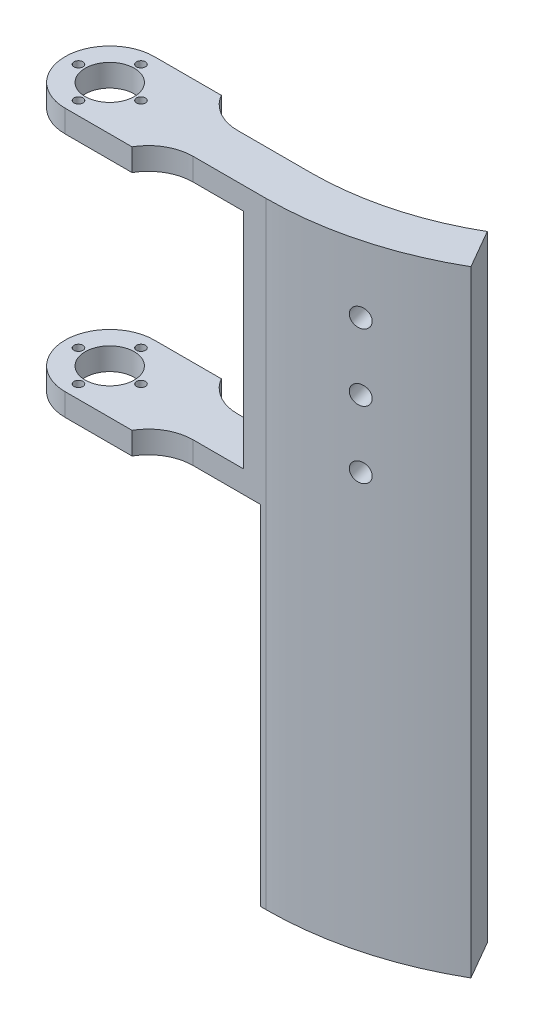
SolidWorks part; units mm, degrees
ref_plane "Front Plane" through (0, 0, 0) normal (0, 0, 1) x (1, 0, 0)
ref_plane "Top Plane" through (0, 0, 0) normal (0, 1, 0) x (1, 0, 0)
ref_plane "Right Plane" through (0, 0, 0) normal (1, 0, 0) x (0, 0, -1)
sketch "Sketch1" plane through (0, 0, 0) normal (0, 0, 1) x (1, 0, 0)
  line L0 (-25, 30) -> (25, 30)
  line L1 (-20, 25) -> (20, 25)
  line L3 (-20, -25) -> (20, -25)
  line L4 (20, 25) -> (20, -25)
  line L5 (-20, 25) -> (20, -25) construction
  line L6 (-20, -25) -> (20, 25) construction
  line L7 (25, 30) -> (25, -30)
  line L8 (-25, -30) -> (25, -30)
  line L9 (-25, 30) -> (-25, 25)
  line L10 (-20, 25) -> (-25, 25)
  line L11 (-20, -25) -> (-25, -25)
  line L12 (-25, -25) -> (-25, -30)
  line L13 (-25, 30) -> (-25, -30) construction
  line L14 (-20, 25) -> (-20, -25) construction
  point P0 (0, 0)
  dimension "D1" = 40
  dimension "D2" = 50
  dimension "D3" = 5
extrude "Boss-Extrude2" add sketch "Sketch1" along normal blind 20
fillet "Fillet1" 2 edges at (-25, 27.5, 20) (-25, 27.5, 0) type full round first side face at (-1.25, 0, 20) second side face at (-1.25, 0, 0) middle face at (-25, 27.5, 10)
fillet "Fillet2" 2 edges at (-25, -27.5, 20) (-25, -27.5, 0) type full round first side face at (1.25, 0, 20) second side face at (1.25, 0, 0) middle face at (-25, -27.5, 10)
sketch "Sketch5" plane through (0, 30, 0) normal (0, 1, 0) x (1, 0, 0)
  circle A0 centre (-15, -10) radius 7 construction
  circle A1 centre (-15, -3) radius 1
  circle A2 centre (-22, -10) radius 1
  circle A3 centre (-15, -17) radius 1
  circle A4 centre (-8, -10) radius 1
  circle A5 centre (-15, -10) radius 5.5
  dimension "D1" = 14
  dimension "D2" = 2
  dimension "D3" = 11
extrude "Cut-Extrude5" cut sketch "Sketch5" against normal through all
sketch "Sketch10" plane through (25, 0, 0) normal (1, 0, 0) x (0, 0, -1)
  line L1 (-15, 28.1801) -> (-15, -28.1801)
  line L3 (-20, -30) -> (-20, 30) construction
  line L4 (-10, 30) -> (-10, 19.211) construction
  line L5 (-20, 30) -> (0, 30) construction
  line L7 (-5, 28.1801) -> (-5, -28.1801)
  line L9 (0, -30) -> (0, 30) construction
  line L10 (0, -30) -> (0, 30)
  line L11 (-20, -30) -> (-20, 30)
  line L12 (-15, 28.1801) -> (-15, 30)
  line L13 (-15, 30) -> (-20, 30)
  line L14 (-15, -28.1801) -> (-15, -30)
  line L15 (-20, -30) -> (0, -30) construction
  line L16 (-15, -30) -> (-20, -30)
  line L17 (-5, -28.1801) -> (-5, -30)
  line L18 (-5, -30) -> (0, -30)
  line L19 (-5, 28.1801) -> (-5, 30)
  line L20 (-5, 30) -> (0, 30)
  dimension "D2" = 5
extrude "Cut-Extrude7" cut sketch "Sketch10" against normal blind 25
fillet "Fillet5" radius 10 4 edges at (0, 27.5, 15) (0, 27.5, 5) (0, -27.5, 15) (0, -27.5, 5)
sketch "Sketch12" plane through (0, -30, 0) normal (0, -1, 0) x (1, 0, 0)
  line L0 (56.2263, -3.3597) -> (61.2225, 5.3027)
  line L1 (25, 15) -> (25, 5)
  arc A0 (56.2263, -3.3597) -> (25, 5) centre (25, -57.5) ccw
  arc A1 (61.2225, 5.3027) -> (25, 15) centre (25, -57.5) ccw
extrude "Boss-Extrude5" add sketch "Sketch12" against normal up to surface (60 mm away) up to face at (-16, 30, 3)
ref_plane "Plane1" through (2.921, 0, 10.9109) normal (-0.2586, 0, -0.966) x (-0.966, 0, 0.2586)
sketch "Sketch13" plane through (2.921, 0, 10.9109) normal (-0.2586, 0, -0.966) x (-0.966, 0, 0.2586)
  line L0 (-39.0195, 30) -> (-39.0195, 0) construction
  line L1 (-22.8565, 30) -> (-55.1825, 30) construction
  line L2 (-39.0195, 0) -> (-39.0195, -30) construction
  line L3 (-55.1825, -30) -> (-22.8565, -30) construction
  circle A0 centre (-39.0195, 15) radius 2.1
  circle A1 centre (-39.0195, 0) radius 2.1
  circle A2 centre (-39.0195, -15) radius 2.1
  dimension "D1" = 4.2
extrude "Cut-Extrude8" cut sketch "Sketch13" against normal blind 60
ref_plane "Plane2" through (4.3924, 0, 18.6716) normal (-0.229, 0, -0.9734) x (-0.9734, 0, 0.229)
ref_plane "Plane3" through (5.1366, 0, 21.8352) normal (-0.229, 0, -0.9734) x (-0.9734, 0, 0.229)
sketch "Sketch14" plane through (0, -30, 0) normal (0, -1, 0) x (1, 0, 0)
  line L0 (61.2225, 5.3027) -> (56.2263, -3.3597)
  line L1 (25, 5) -> (23.7675, 5)
  line L2 (23.7675, 5) -> (23.7675, 15)
  line L3 (23.7675, 15) -> (25, 15)
  arc A0 (56.2263, -3.3597) -> (25, 5) centre (25, -57.5) ccw
  arc A1 (61.2225, 5.3027) -> (25, 15) centre (25, -57.5) ccw
  point P10 (0, 0)
  point P15 (0, 0)
extrude "Boss-Extrude6" add sketch "Sketch14" along normal blind 78
equation "\"éà\"=10"
